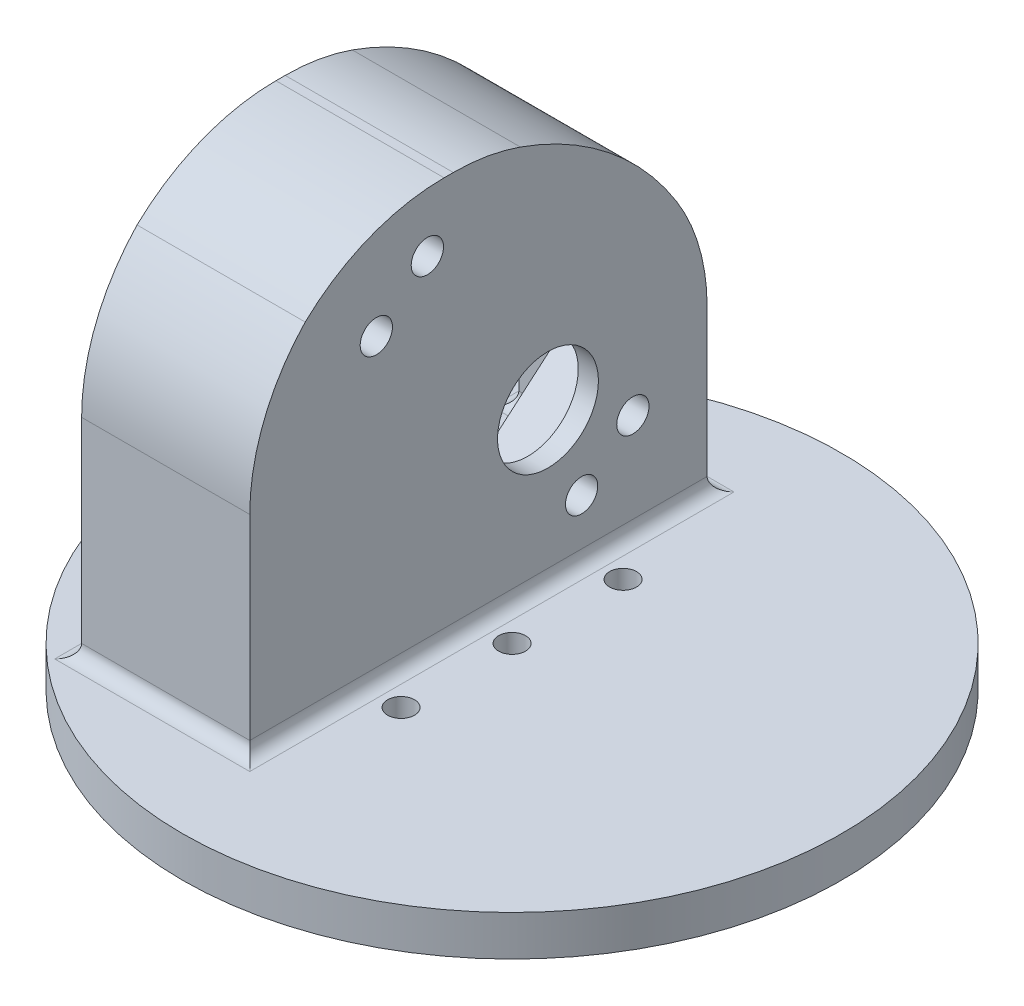
SolidWorks part; units mm, degrees
ref_plane "Front Plane" through (0, 0, 0) normal (0, 0, 1) x (1, 0, 0)
ref_plane "Top Plane" through (0, 0, 0) normal (0, 1, 0) x (1, 0, 0)
ref_plane "Right Plane" through (0, 0, 0) normal (1, 0, 0) x (0, 0, -1)
sketch "Sketch1" plane through (0, 0, 0) normal (0, 1, 0) x (1, 0, 0)
  circle A0 centre (0, 0) radius 49
  circle A1 centre (0, 16.5) radius 2
  circle A4 centre (0, -16.5) radius 2
  circle A5 centre (0, 0) radius 2
  dimension "D1" = 98
  dimension "D9" = 4
  dimension "D2" = 33
  dimension "D5" = 16.5
extrude "Boss-Extrude1" add sketch "Sketch1" along normal blind 6
sketch "Sketch3" plane through (0, 6, 0) normal (0, 1, 0) x (1, 0, 0)
  line L1 (-30, 34) -> (-5, 34)
  line L2 (-30, 34) -> (-30, -34)
  line L3 (-30, -34) -> (-5, -34)
  line L4 (-5, 34) -> (-5, -34)
  dimension "D1" = 5
  dimension "D2" = 30
  dimension "D3" = 34
  dimension "D4" = 34
extrude "Boss-Extrude2" add sketch "Sketch3" along normal blind 60
sketch "Sketch4" plane through (-30, 0, 0) normal (-1, 0, 0) x (0, 0, 1)
  line L0 (-13.8251, 9) -> (-29, 22.0277)
  line L1 (-29, 22.0277) -> (6.1749, 63)
  line L2 (6.1749, 63) -> (21.3498, 49.9723)
  line L3 (21.3498, 49.9723) -> (-13.8251, 9)
  line L4 (-34, 66) -> (-34, 6) construction
  line L8 (-34, 6) -> (34, 6) construction
  line L11 (-34, 66) -> (34, 66) construction
  dimension "D1" = 20
  dimension "D2" = 3
  dimension "D3" = 5
  dimension "D5" = 54
  dimension "D6" = 3
extrude "Cut-Extrude1" cut sketch "Sketch4" against normal blind 14
sketch "Sketch5" plane through (-16, 0, 0) normal (-1, 0, 0) x (0, 0, 1)
  line L0 (-24.4403, 27.339) -> (-9.2654, 14.3112)
  line L1 (-9.2654, 14.3112) -> (16.7901, 44.661)
  line L2 (16.7901, 44.661) -> (1.6152, 57.6888)
  line L3 (1.6152, 57.6888) -> (-24.4403, 27.339)
  line L4 (21.3498, 49.9723) -> (6.1749, 63) construction
  line L5 (-29, 22.0277) -> (-13.8251, 9) construction
  line L6 (6.1749, 63) -> (-29, 22.0277) construction
  line L7 (-15.3391, 14.9126) -> (15.1827, 50.6539) construction
  line L8 (-29, 22.0277) -> (-13.8251, 9) construction
  line L9 (-22.9605, 21.3867) -> (7.5952, 57.1678) construction
  line L11 (-13.8251, 9) -> (21.3498, 49.9723) construction
  circle A0 centre (-22.9605, 21.3867) radius 2.4
  circle A1 centre (-15.3391, 14.9126) radius 2.4
  circle A2 centre (7.5952, 57.1678) radius 2.4
  circle A3 centre (15.1827, 50.6539) radius 2.4
  dimension "D7" = 4.8
  dimension "D8" = 4.8
  dimension "D9" = 4.8
  dimension "D10" = 4.8
  dimension "D1" = 7
  dimension "D2" = 7
  dimension "D3" = 0
  dimension "D4" = 0
  dimension "D5" = 10
  dimension "D6" = 5
  dimension "D11" = 3.5
  dimension "D12" = 3.5524
  dimension "D13" = 10
  dimension "D15" = 3.5
  dimension "D16" = 3.5
extrude "Cut-Extrude2" cut sketch "Sketch5" against normal blind 20
sketch "Sketch8" plane through (-30, 0, 0) normal (-1, 0, 0) x (0, 0, 1)
  line L1 (34, 66) -> (34, 6) construction
  line L2 (-34, 66) -> (34, 66) construction
  line L3 (-34, 66) -> (-34, 6) construction
  line L4 (-34, 36) -> (-34, 66)
  line L5 (-34, 66) -> (0, 66)
  line L6 (14.5, 66) -> (34, 66)
  line L7 (34, 66) -> (34, 46.5)
  arc A1 (14.5, 66) -> (34, 46.5) centre (-6.0392, 25.9608) cw
  arc A2 (-34, 36) -> (0, 66) centre (8.7183, 21.8526) cw
  dimension "D2" = 45
  dimension "D3" = 45
  dimension "D4" = 19.5
  dimension "D5" = 19.5
  dimension "D6" = 34
  dimension "D7" = 30
extrude "Cut-Extrude3" cut sketch "Sketch8" against normal blind 30
sketch "Sketch12" plane through (-30, 0, 0) normal (-1, 0, 0) x (0, 0, 1)
  line L0 (-31, 6) -> (-31, 36)
  line L1 (-34, 6) -> (34, 6) construction
  line L2 (0, 63) -> (14.5, 63)
  line L3 (31, 46.5) -> (31, 6)
  line L4 (-34, 36) -> (-34, 6) construction
  line L5 (-31, 6) -> (31, 6)
  arc A0 (-31, 36) -> (0, 63) centre (10.7917, 19.3132) cw
  arc A1 (14.5, 63) -> (31, 46.5) centre (-7.9817, 24.0183) cw
  dimension "D3" = 45
  dimension "D7" = 45
  dimension "D1" = 3
  dimension "D2" = 30
  dimension "D4" = 0
  dimension "D5" = 3
  dimension "D6" = 14.5
  dimension "D8" = 3
  dimension "D9" = 0
extrude "Cut-Extrude5" cut sketch "Sketch12" against normal blind 10
sketch "Sketch13" plane through (-5, 0, 0) normal (1, 0, 0) x (0, 0, -1)
  line L0 (-1.6152, 57.6888) -> (-16.7901, 44.661)
  line L1 (-16.7901, 44.661) -> (9.2654, 14.3112)
  line L2 (9.2654, 14.3112) -> (24.4403, 27.339)
  line L3 (24.4403, 27.339) -> (-1.6152, 57.6888)
  circle A0 centre (10.339, 28.4125) radius 7.5
  dimension "D2" = 15
  dimension "D1" = 10
  dimension "D3" = 10
extrude "Boss-Extrude3" add sketch "Sketch13" against normal blind 3
fillet "Fillet2" radius 30 4 edges at (-17.5, 46.5, 34) (-17.5, 66, 14.5) (-17.5, 66, 0) (-17.5, 36, -34)
fillet "Fillet3" radius 2 8 edges at (-17.5, 6, 34) (-30, 6, 32.5) (-25, 6, 31) (-20, 6, 0) (-25, 6, -31) (-30, 6, -32.5) (-5, 6, 0) (-17.5, 6, -34)
fillet "Fillet4" radius 4 4 edges at (-25, 36, -31) (-25, 63, 0) (-25, 63, 14.5) (-25, 46.5, 31)
